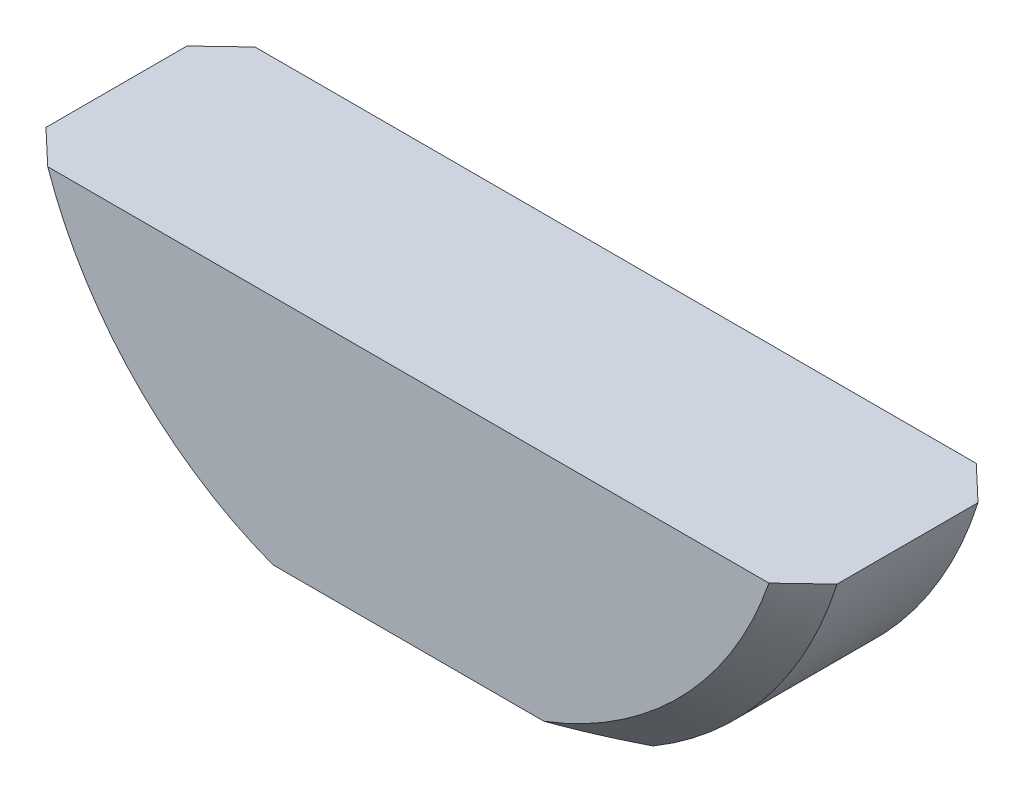
SolidWorks part; units mm, degrees
ref_plane "Front" through (0, 0, 0) normal (0, 0, 1) x (1, 0, 0)
ref_plane "Top" through (0, 0, 0) normal (0, 1, 0) x (1, 0, 0)
ref_plane "Right" through (0, 0, 0) normal (1, 0, 0) x (0, 0, -1)
sketch "Sketch1" plane through (0, 0, 0) normal (0, 0, 1) x (1, 0, 0)
  line L0 (-1.9079, 0) -> (1.9079, 0)
  arc A0 (-1.9079, 0) -> (1.9079, 0) centre (0, 0.6) ccw
extrude "Extrude1" add sketch "Sketch1" along normal blind 1
sketch "Sketch2" plane through (0, 0, 0) normal (0, 0, 1) x (1, 0, 0)
  line L0 (-1.9079, -1.12) -> (1.9079, -1.12)
  line L1 (1.9079, 0) -> (-1.9079, 0) construction
extrude "Cut-Extrude1" cut sketch "Sketch2" against normal through all and the other way through all flip side to cut
chamfer "Chamfer1" distance 0.16 angle 45 4 edges at (-1.5677, -0.6419, 0) (1.5677, -0.6419, 0) (1.5677, -0.6419, 1) (-1.5677, -0.6419, 1)
equation "\"h2@Sketch2\" = 0.8 * \"h1@Sketch1\""
